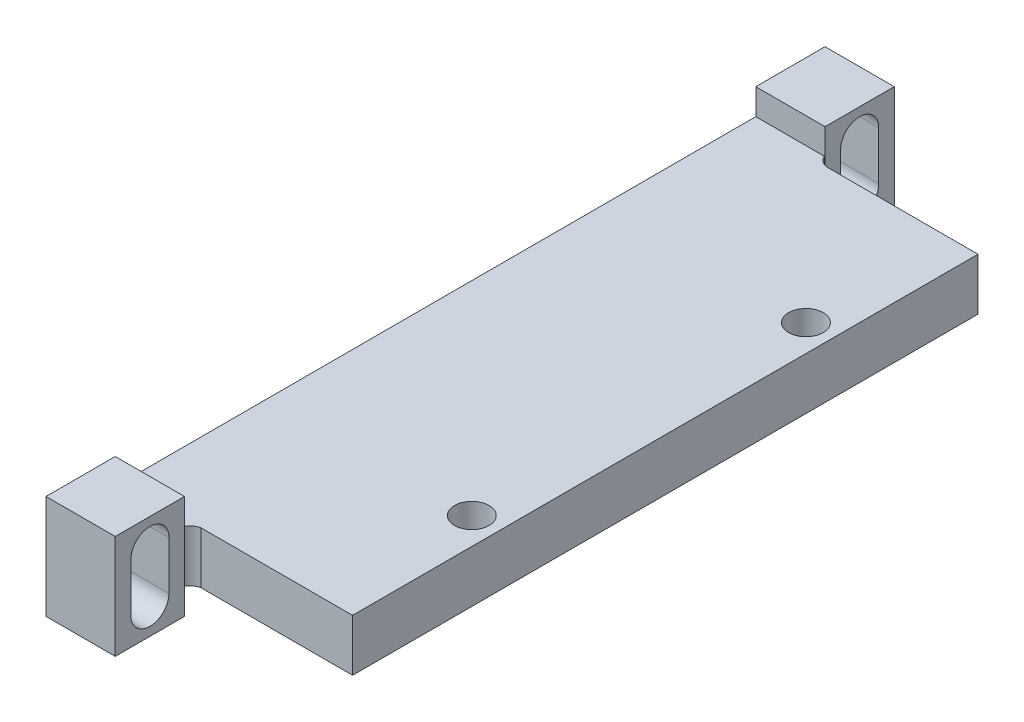
SolidWorks part; units mm, degrees
ref_plane "Plan de face" through (0, 0, 0) normal (0, 0, 1) x (1, 0, 0)
ref_plane "Plan de dessus" through (0, 0, 0) normal (0, 1, 0) x (1, 0, 0)
ref_plane "Plan de droite" through (0, 0, 0) normal (1, 0, 0) x (0, 0, -1)
sketch "Esquisse1" plane through (0, 0, 0) normal (0, 1, 0) x (1, 0, 0)
  line L0 (2, 18.5) -> (-2, 18.5)
  line L1 (2, 18.5) -> (2, 22.5)
  line L2 (2, 22.5) -> (-2, 22.5)
  line L3 (-2, 18.5) -> (-2, 22.5)
  line L4 (2, -22.5) -> (-2, -22.5)
  line L5 (-2, -18.5) -> (-2, -22.5)
  line L6 (2, -18.5) -> (-2, -18.5)
  line L7 (2, -18.5) -> (2, -22.5)
  dimension "D1" = 4
  dimension "D2" = 4
extrude "Boss.-Extru.1" add sketch "Esquisse1" along normal blind 3 and the other way blind 3
sketch "Esquisse2" plane through (0, 0, 0) normal (0, 1, 0) x (1, 0, 0)
  line L0 (2, 18.5) -> (2, 22.5) construction
  line L1 (1.93, 18.5716) -> (-2, 18.5716)
  line L2 (-2, 22.5) -> (-2, 18.5) construction
  line L3 (1.93, -18.6273) -> (-2, -18.5898)
  line L4 (-2, -18.5) -> (-2, -22.5) construction
  line L5 (-2, -18.5898) -> (-2, 18.5716)
  point P2 (1.93, 18.5716)
  line B0 (2.5362, 18.0358) -> (11.3006, 18.0358)
  line B1 (11.3006, 18.0358) -> (11.3006, -18.0915)
  line B2 (2.5362, -18.0915) -> (11.3006, -18.0915)
  spline B3 degree 2 poles (1.93, 18.5716) (2.0881, 18.1442) (2.5362, 18.0358) knots 0 0 0 1 1 1
  spline B4 degree 2 poles (1.93, -18.6273) (2.0881, -18.1999) (2.5362, -18.0915) knots 0 0 0 1 1 1
  dimension "D1" = 0.07
sketch_block_instance "Bloc1-1"
sketch_block "Bloc1" parameters "D1"=9.6644
sketch "Esquisse3" plane through (0, 0, 0) normal (0, 1, 0) x (1, 0, 0)
  line L0 (-2, 18.5716) -> (1.93, 18.5716)
  line L1 (2.5362, 18.0358) -> (11.3006, 18.0358)
  line L2 (11.3006, 18.0358) -> (11.3006, -18.0915)
  line L3 (11.3006, -18.0915) -> (2.5362, -18.0915)
  line L4 (1.93, -18.6273) -> (-2, -18.6273)
  line L5 (-2, -18.6273) -> (-2, 18.5716)
  spline S0 degree 2 poles (1.93, 18.5716) (2.0881, 18.1442) (2.5362, 18.0358) knots 0 0 0 1 1 1
  spline S1 degree 2 poles (2.5362, -18.0915) (2.0881, -18.1999) (1.93, -18.6273) knots 0 0 0 1 1 1
extrude "Boss.-Extru.2" add sketch "Esquisse3" along normal blind 1.5 and the other way blind 1.5
sketch "Esquisse4" plane through (0, 1.5, 0) normal (0, 1, 0) x (1, 0, 0)
  line L0 (8.75, 9.6459) -> (8.75, -9.6541) construction
  line L1 (2, 18.5) -> (2, 22.5) construction
  circle A0 centre (9.75, 9.6459) radius 1
  circle A1 centre (9.75, -9.6541) radius 1
  dimension "D1" = 6.75
extrude "Enlèv. mat.-Extru.1" cut sketch "Esquisse4" against normal blind 21.5
sketch "Esquisse5" plane through (2, 0, 0) normal (1, 0, 0) x (0, 0, -1)
  line L0 (-20.5, 1.4) -> (-20.5, -1.4) construction
  line L1 (-19.4, 1.4) -> (-19.4, -1.4)
  line L2 (-21.6, 1.4) -> (-21.6, -1.4)
  line L3 (-18.5, -3) -> (-18.5, 3) construction
  line L4 (-22.5, 3) -> (-18.5, 3) construction
  line L5 (0, 3.3) -> (0, -3.3) construction
  line L6 (20.5, 1.4) -> (20.5, -1.4) construction
  line L7 (19.4, 1.4) -> (19.4, -1.4)
  line L8 (21.6, 1.4) -> (21.6, -1.4)
  arc A0 (-19.4, 1.4) -> (-21.6, 1.4) centre (-20.5, 1.4) ccw
  arc A1 (-21.6, -1.4) -> (-19.4, -1.4) centre (-20.5, -1.4) ccw
  arc A2 (19.4, 1.4) -> (21.6, 1.4) centre (20.5, 1.4) cw
  arc A3 (21.6, -1.4) -> (19.4, -1.4) centre (20.5, -1.4) cw
  point P2 (-20.5, 0)
  point P15 (20.5, 0)
  dimension "D1" = 2
  dimension "D2" = 1.6
  dimension "D3" = 2.8
extrude "Enlèv. mat.-Extru.2" cut sketch "Esquisse5" against normal blind 21.5
